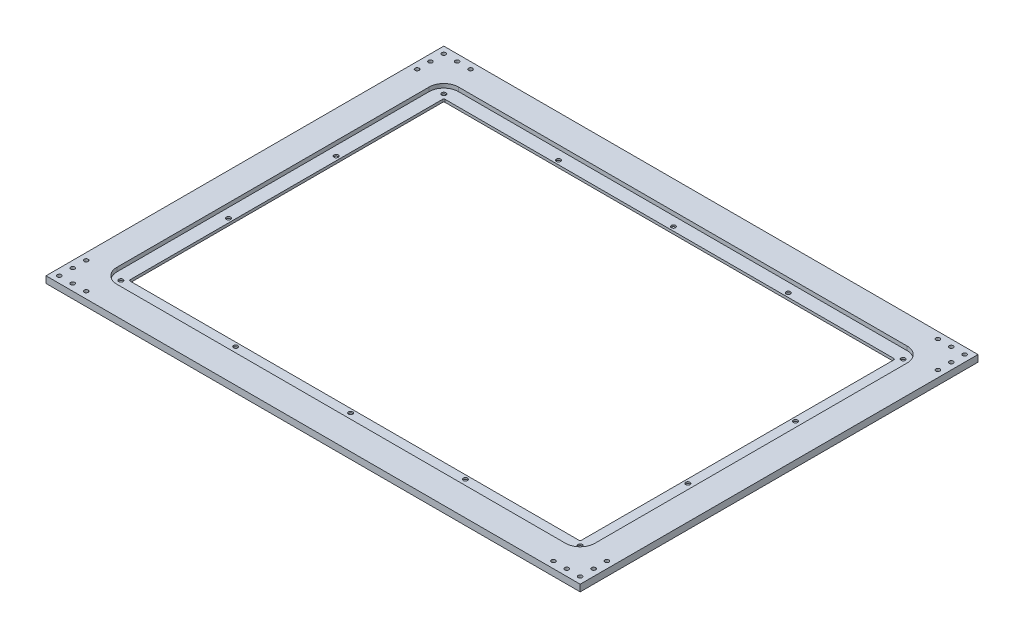
SolidWorks part; units mm, degrees
ref_plane "Front Plane" through (0, 0, 0) normal (0, 0, 1) x (1, 0, 0)
ref_plane "Top Plane" through (0, 0, 0) normal (0, 1, 0) x (1, 0, 0)
ref_plane "Right Plane" through (0, 0, 0) normal (1, 0, 0) x (0, 0, -1)
sketch "Sketch1" plane through (0, 0, 0) normal (0, 1, 0) x (1, 0, 0)
  line L1 (0, 0) -> (399.5, 0)
  line L2 (0, 0) -> (0, 297.5)
  line L3 (0, 297.5) -> (399.5, 297.5)
  line L4 (399.5, 0) -> (399.5, 297.5)
  dimension "D1" = 297.5
  dimension "D2" = 399.5
extrude "Boss-Extrude1" add sketch "Sketch1" along normal blind 5
sketch "Sketch2" plane through (0, 0, 0) normal (0, -1, 0) x (1, 0, 0)
  line L0 (399.5, 0) -> (0, 0)
  line L1 (199.75, 0) -> (199.75, -297.5)
  line L2 (399.5, -297.5) -> (0, -297.5) construction
  line L3 (0, -297.5) -> (0, 0)
  line L4 (0, -148.75) -> (399.5, -148.75)
  line L5 (399.5, 0) -> (399.5, -297.5) construction
  circle A0 centre (31, -5) radius 1.6 construction
  circle A1 centre (10, -5) radius 1.6 construction
  circle A2 centre (5, -10) radius 1.6 construction
  circle A3 centre (5, -31) radius 1.6 construction
  circle A4 centre (31, -5) radius 1.6
  circle A5 centre (10, -5) radius 1.6
  circle A6 centre (5, -10) radius 1.6
  circle A7 centre (5, -31) radius 1.6
  circle A8 centre (394.5, -31) radius 1.6
  circle A9 centre (394.5, -10) radius 1.6
  circle A10 centre (389.5, -5) radius 1.6
  circle A11 centre (368.5, -5) radius 1.6
  circle A12 centre (31, -292.5) radius 1.6
  circle A13 centre (10, -292.5) radius 1.6
  circle A14 centre (5, -287.5) radius 1.6
  circle A15 centre (5, -266.5) radius 1.6
  circle A16 centre (368.5, -292.5) radius 1.6
  circle A17 centre (389.5, -292.5) radius 1.6
  circle A18 centre (394.5, -287.5) radius 1.6
  circle A19 centre (394.5, -266.5) radius 1.6
extrude "Cut-Extrude2" cut sketch "Sketch2" against normal blind 1.2 contours A4 | A5 | A6 | A7 | A8 | A9 | A10 | A11 | A12 | A13 | A14 | A15 | A18 | A17 | A16 | A19
sketch "Sketch3" plane through (0, 0, 0) normal (0, -1, 0) x (1, 0, 0)
  circle A0 centre (25, -5) radius 1.5 construction
  circle A1 centre (15, -5) radius 1.5 construction
  circle A2 centre (5, -15) radius 1.5 construction
  circle A3 centre (5, -25) radius 1.5 construction
  circle A4 centre (5, -272.5) radius 1.5 construction
  circle A5 centre (5, -282.5) radius 1.5 construction
  circle A6 centre (15, -292.5) radius 1.5 construction
  circle A7 centre (25, -292.5) radius 1.5 construction
  circle A8 centre (374.5, -5) radius 1.5 construction
  circle A9 centre (384.5, -5) radius 1.5 construction
  circle A10 centre (394.5, -15) radius 1.5 construction
  circle A11 centre (394.5, -25) radius 1.5 construction
  circle A12 centre (394.5, -272.5) radius 1.5 construction
  circle A13 centre (394.5, -282.5) radius 1.5 construction
  circle A14 centre (384.5, -292.5) radius 1.5 construction
  circle A15 centre (374.5, -292.5) radius 1.5 construction
  circle A16 centre (25, -5) radius 1.5
  circle A17 centre (15, -5) radius 1.5
  circle A18 centre (5, -15) radius 1.5
  circle A19 centre (5, -25) radius 1.5
  circle A20 centre (5, -272.5) radius 1.5
  circle A21 centre (5, -282.5) radius 1.5
  circle A22 centre (15, -292.5) radius 1.5
  circle A23 centre (25, -292.5) radius 1.5
  circle A24 centre (374.5, -5) radius 1.5
  circle A25 centre (384.5, -5) radius 1.5
  circle A26 centre (394.5, -15) radius 1.5
  circle A27 centre (394.5, -25) radius 1.5
  circle A28 centre (394.5, -272.5) radius 1.5
  circle A29 centre (394.5, -282.5) radius 1.5
  circle A30 centre (384.5, -292.5) radius 1.5
  circle A31 centre (374.5, -292.5) radius 1.5
extrude "Cut-Extrude3" cut sketch "Sketch3" against normal blind 59.2
sketch "Sketch4" plane through (0, 5, 0) normal (0, 1, 0) x (1, 0, 0)
  circle A0 centre (5, 5) radius 1.5 construction
  circle A1 centre (394.5, 292.5) radius 1.5 construction
  circle A2 centre (394.5, 5) radius 1.5 construction
  circle A3 centre (5, 292.5) radius 1.5 construction
  circle A4 centre (5, 5) radius 1.5
  circle A5 centre (394.5, 292.5) radius 1.5
  circle A6 centre (394.5, 5) radius 1.5
  circle A7 centre (5, 292.5) radius 1.5
extrude "Cut-Extrude4" cut sketch "Sketch4" against normal blind 10.2
sketch "Sketch5" plane through (0, 5, 0) normal (0, 1, 0) x (1, 0, 0)
  line L0 (0, 297.5) -> (0, 0) construction
  line L1 (32, 276.5) -> (367.5, 276.5)
  line L2 (21, 265.5) -> (21, 32)
  line L3 (32, 21) -> (367.5, 21)
  line L4 (378.5, 265.5) -> (378.5, 32)
  line L5 (399.5, 297.5) -> (0, 297.5) construction
  line L6 (399.5, 0) -> (399.5, 297.5) construction
  line L7 (0, 0) -> (399.5, 0) construction
  arc A0 (378.5, 32) -> (367.5, 21) centre (367.5, 32) cw
  arc A1 (378.5, 265.5) -> (367.5, 276.5) centre (367.5, 265.5) ccw
  arc A2 (32, 276.5) -> (21, 265.5) centre (32, 265.5) ccw
  arc A3 (21, 32) -> (32, 21) centre (32, 32) ccw
  dimension "D5" = 11
  dimension "D1" = 21
  dimension "D2" = 21
  dimension "D3" = 21
  dimension "D4" = 21
extrude "Cut-Extrude5" cut sketch "Sketch5" against normal blind 3
sketch "Sketch6" plane through (0, 2, 0) normal (0, 1, 0) x (1, 0, 0)
  line L0 (368.5, 32) -> (368.5, 265.5)
  line L1 (367.5, 266.5) -> (32, 266.5)
  line L2 (31, 265.5) -> (31, 32)
  line L3 (32, 31) -> (367.5, 31)
  line L4 (378.5, 32) -> (378.5, 265.5)
  line L5 (367.5, 276.5) -> (32, 276.5)
  line L6 (21, 265.5) -> (21, 32)
  line L7 (32, 21) -> (367.5, 21)
  line L8 (378.5, 32) -> (378.5, 265.5)
  line L9 (367.5, 276.5) -> (32, 276.5)
  line L10 (21, 265.5) -> (21, 32)
  line L11 (32, 21) -> (367.5, 21)
  arc A0 (367.5, 31) -> (368.5, 32) centre (367.5, 32) ccw
  arc A1 (368.5, 265.5) -> (367.5, 266.5) centre (367.5, 265.5) ccw
  arc A2 (32, 266.5) -> (31, 265.5) centre (32, 265.5) ccw
  arc A3 (31, 32) -> (32, 31) centre (32, 32) ccw
  arc A4 (367.5, 21) -> (378.5, 32) centre (367.5, 32) ccw
  arc A5 (378.5, 265.5) -> (367.5, 276.5) centre (367.5, 265.5) ccw
  arc A6 (32, 276.5) -> (21, 265.5) centre (32, 265.5) ccw
  arc A7 (21, 32) -> (32, 21) centre (32, 32) ccw
  arc A8 (367.5, 21) -> (378.5, 32) centre (367.5, 32) ccw
  arc A9 (378.5, 265.5) -> (367.5, 276.5) centre (367.5, 265.5) ccw
  arc A10 (32, 276.5) -> (21, 265.5) centre (32, 265.5) ccw
  arc A11 (21, 32) -> (32, 21) centre (32, 32) ccw
  point P24 (32, 31)
  dimension "D1" = 0
  dimension "D2" = 10
extrude "Cut-Extrude6" cut sketch "Sketch6" against normal blind 13 contours L1 A2 L2 A3 L3 A0 L0 A1
sketch "Sketch9" plane through (0, 2, 0) normal (0, 1, 0) x (1, 0, 0)
  circle A0 centre (199.75, 28) radius 1.6 construction
  circle A1 centre (285.625, 28) radius 1.6 construction
  circle A2 centre (371.5, 28) radius 1.6 construction
  circle A3 centre (371.5, 108.5) radius 1.6 construction
  circle A4 centre (371.5, 189) radius 1.6 construction
  circle A5 centre (113.875, 28) radius 1.6 construction
  circle A6 centre (28, 28) radius 1.6 construction
  circle A7 centre (28, 108.5) radius 1.6 construction
  circle A8 centre (28, 189) radius 1.6 construction
  circle A9 centre (28, 269.5) radius 1.6 construction
  circle A10 centre (113.875, 269.5) radius 1.6 construction
  circle A11 centre (199.75, 269.5) radius 1.6 construction
  circle A12 centre (285.625, 269.5) radius 1.6 construction
  circle A13 centre (371.5, 269.5) radius 1.6 construction
  circle A14 centre (199.75, 28) radius 1.6
  circle A15 centre (285.625, 28) radius 1.6
  circle A16 centre (371.5, 28) radius 1.6
  circle A17 centre (371.5, 108.5) radius 1.6
  circle A18 centre (371.5, 189) radius 1.6
  circle A19 centre (113.875, 28) radius 1.6
  circle A20 centre (28, 28) radius 1.6
  circle A21 centre (28, 108.5) radius 1.6
  circle A22 centre (28, 189) radius 1.6
  circle A23 centre (28, 269.5) radius 1.6
  circle A24 centre (113.875, 269.5) radius 1.6
  circle A25 centre (199.75, 269.5) radius 1.6
  circle A26 centre (285.625, 269.5) radius 1.6
  circle A27 centre (371.5, 269.5) radius 1.6
extrude "Cut-Extrude7" cut sketch "Sketch9" against normal blind 1.2
